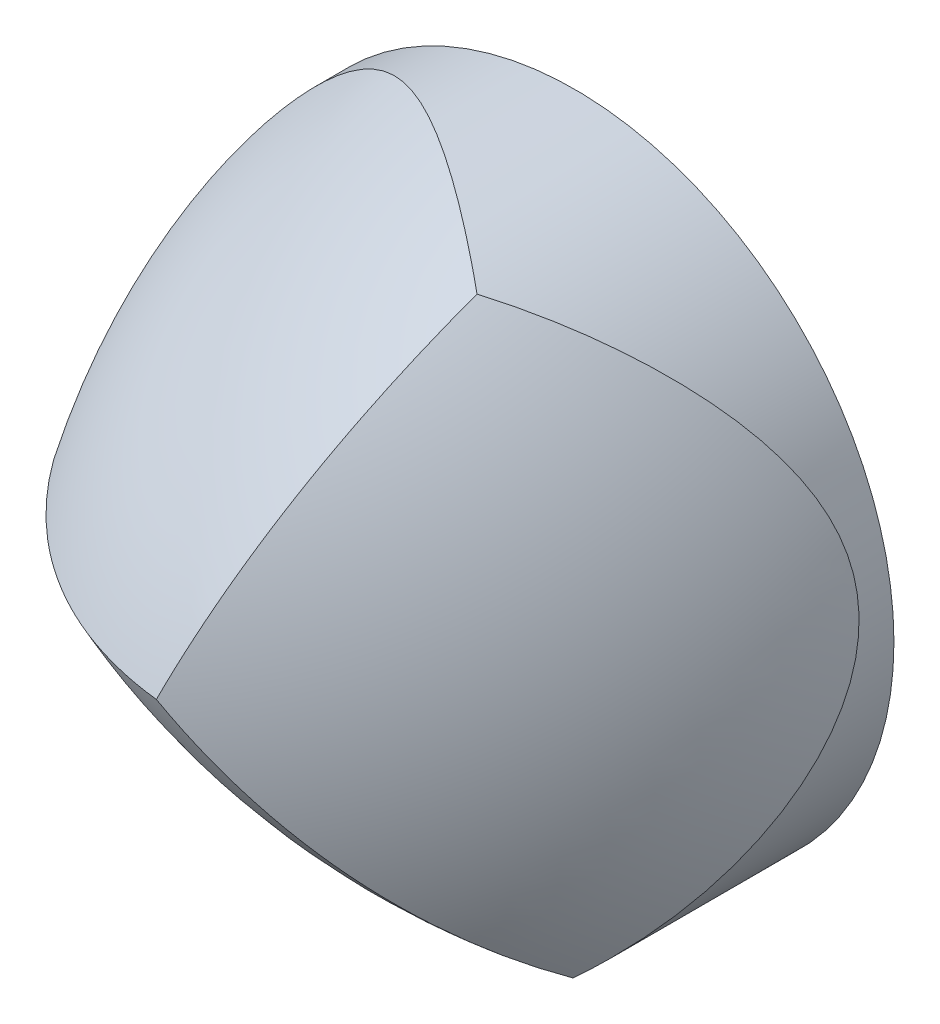
SolidWorks part; units mm, degrees
ref_plane "Front Plane" through (0, 0, 0) normal (0, 0, 1) x (1, 0, 0)
ref_plane "Top Plane" through (0, 0, 0) normal (0, 1, 0) x (1, 0, 0)
ref_plane "Right Plane" through (0, 0, 0) normal (1, 0, 0) x (0, 0, -1)
sketch "Sketch1" plane through (0, 0, 0) normal (0, 0, 1) x (1, 0, 0)
  circle A2 centre (0, 0) radius 152.4
extrude "Boss-Extrude1" add sketch "Sketch1" along normal blind 300
sketch "Sketch2" plane through (0, 0, -90.9) normal (0.766, 0.6428, 0) x (-0.6428, 0.766, 0)
  line L1 (-147.5708, -21.8) -> (-141.1044, -21.8) construction
  line L2 (-144.3376, -21.8) -> (-144.3376, 16.4) construction
  line L3 (-144.3376, -293.6) -> (-144.3376, -593.6)
  line L4 (-144.3376, 326.4) -> (-144.3376, 626.4)
  arc A0 (-144.3376, -293.6) -> (-144.3376, 326.4) centre (-144.3376, 16.4) ccw
  arc A1 (-144.3376, -593.6) -> (-144.3376, 626.4) centre (-144.3376, 16.4) ccw
  circle A2 centre (-144.3376, 16.4) radius 610 construction
  circle A3 centre (-144.3376, 16.4) radius 310 construction
  dimension "D1" = 620
  dimension "D3" = 300
revolve "Cut-Revolve1" cut sketch "Sketch2" angle 360 about L2
pattern_circular "CirPattern1" count 3 every 120 about axis through (0, 0, 300) along (0, 0, -1) of "Cut-Revolve1"
